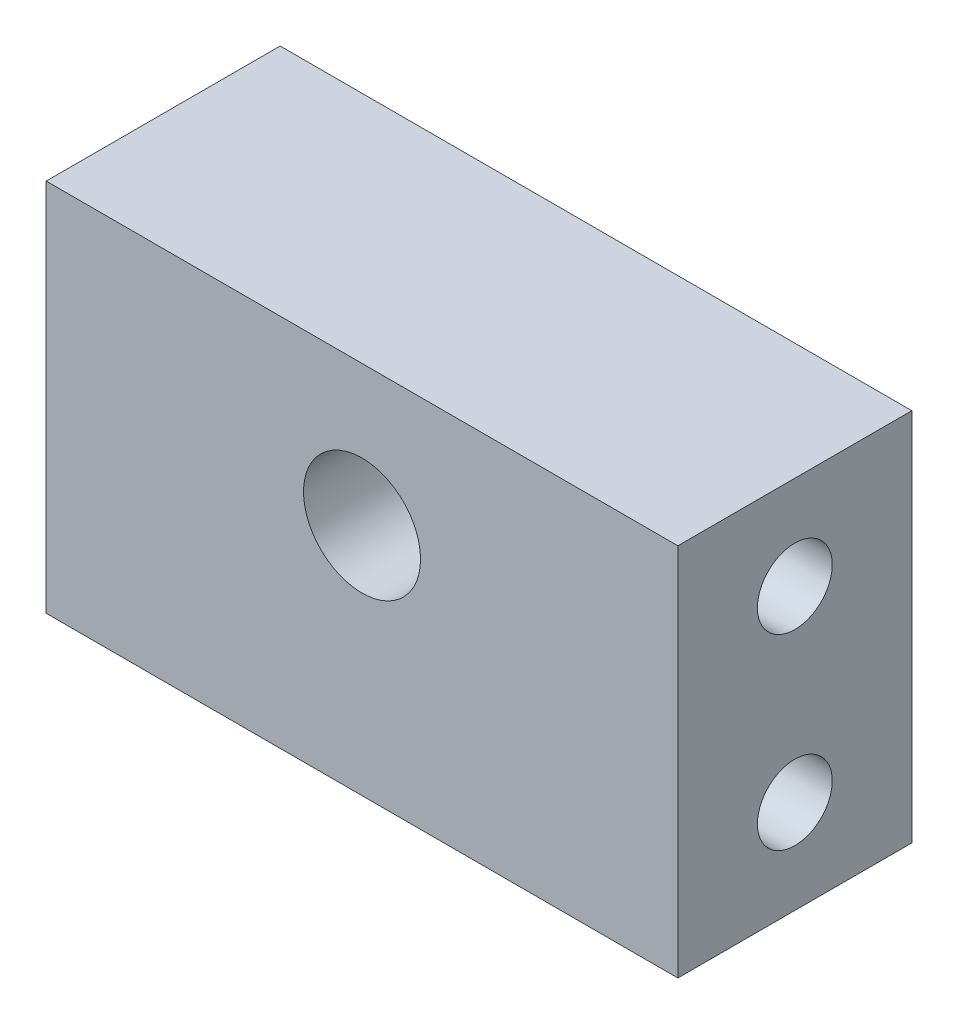
SolidWorks part; units mm, degrees
material "AISI 4130 Acier normalisé à 870C"
ref_plane "Plan de face" through (0, 0, 0) normal (0, 0, 1) x (1, 0, 0)
ref_plane "Plan de dessus" through (0, 0, 0) normal (0, 1, 0) x (1, 0, 0)
ref_plane "Plan de droite" through (0, 0, 0) normal (1, 0, 0) x (0, 0, -1)
sketch "Esquisse1" plane through (0, 0, 0) normal (0, 0, 1) x (1, 0, 0)
  line L1 (0, 0) -> (13.5, 0)
  line L2 (0, 0) -> (0, 8)
  line L3 (0, 8) -> (13.5, 8)
  line L4 (13.5, 0) -> (13.5, 8)
  dimension "D1" = 13.5
  dimension "D2" = 8
extrude "Boss.-Extru.1" add sketch "Esquisse1" along normal blind 5
hole_wizard "Trou pour taraudage pour trou taraudé M21" positions "Esquisse2" profile "Esquisse4" hole size "M2" standard "ISO" end condition through all
sketch "Esquisse2" plane through (0, 0, 0) normal (-1, 0, 0) x (0, 0, 1)
  line L4 (2.5, 6) -> (2.5, 7.5239) construction
  line L6 (0, 8) -> (0, 0) construction
  line L7 (5, 8) -> (5, 0) construction
  line L8 (5, 8) -> (0, 8) construction
  line L9 (0, 4) -> (3.912, 4) construction
  point P0 (2.5, 6)
  point P21 (2.5, 8)
  point P22 (2.5, 2)
  dimension "D1" = 2
sketch "Esquisse4" plane through (0, 6, 2.5) normal (0, 1, 0) x (0, 0, 1)
  line L0 (0, 0) -> (0, 13.5)
  line L1 (0, 13.5) -> (0.8, 13.5)
  line L2 (0.8, 13.5) -> (0.8, 0)
  line L5 (0.8, 0) -> (0, 0)
  line L11 (0, -6.35) -> (0, 107.95) construction
  dimension "Diamètre du perçage jusqu'au prochain" = 1.6
  dimension "Profondeur du perçage jusqu'au prochain" = 13.5
hole_wizard "Trou pour taraudage pour trou taraudé M32" positions "Esquisse5" profile "Esquisse6" hole size "M3" standard "ISO" end condition through all
sketch "Esquisse5" plane through (0, 0, 5) normal (0, 0, 1) x (1, 0, 0)
  line L0 (6.75, 8) -> (6.75, 4.339) construction
  line L1 (13.5, 8) -> (0, 8) construction
  point P0 (6.75, 5)
  dimension "D1" = 3
sketch "Esquisse6" plane through (6.75, 5, 5) normal (1, 0, 0) x (0, -1, 0)
  line L0 (0, 0) -> (0, 5)
  line L1 (0, 5) -> (1.25, 5)
  line L2 (1.25, 5) -> (1.25, 0)
  line L5 (1.25, 0) -> (0, 0)
  line L11 (0, -6.35) -> (0, 107.95) construction
  dimension "Diamètre du perçage jusqu'au prochain" = 2.5
  dimension "Profondeur du perçage jusqu'au prochain" = 5
